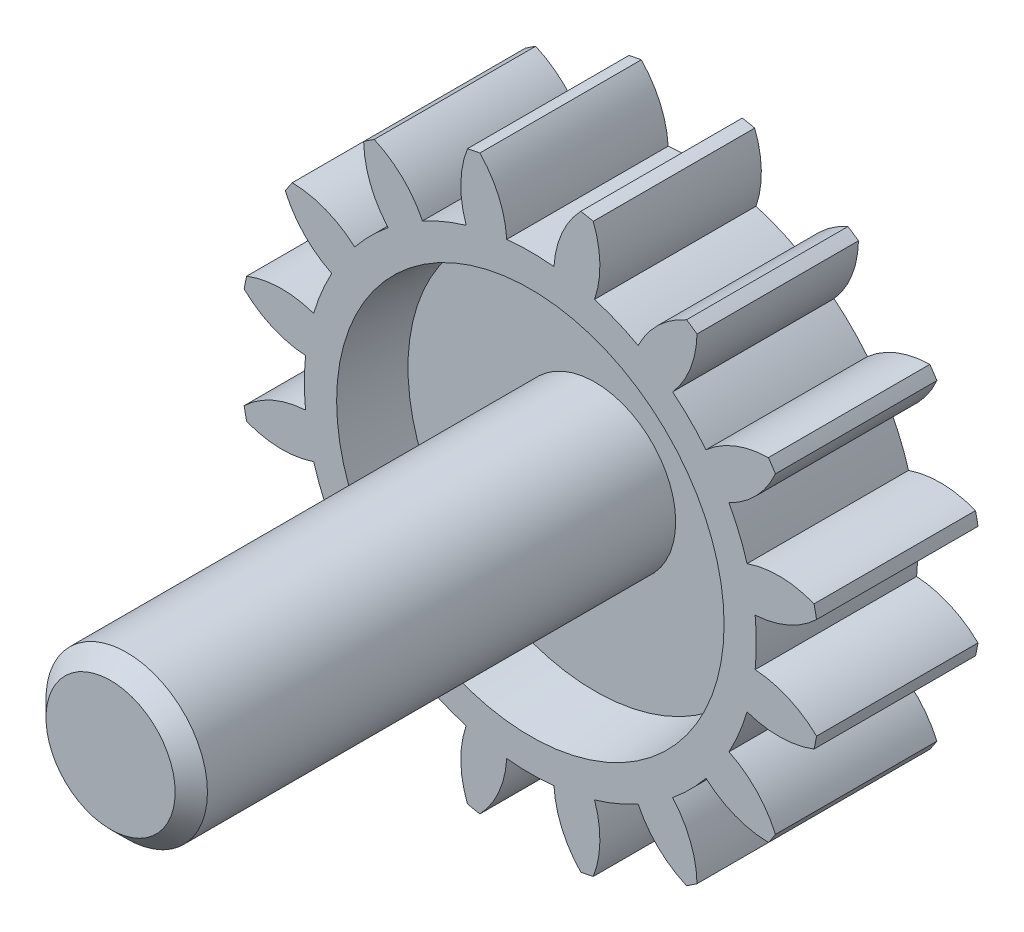
SolidWorks part; units mm, degrees
ref_plane "Спереди" through (0, 0, 0) normal (0, 0, 1) x (1, 0, 0)
ref_plane "Сверху" through (0, 0, 0) normal (0, 1, 0) x (1, 0, 0)
ref_plane "Справа" through (0, 0, 0) normal (1, 0, 0) x (0, 0, -1)
sketch "Эскиз1" plane through (0, 0, 0) normal (0, 0, 1) x (1, 0, 0)
  circle A0 centre (0, 0) radius 18
  dimension "D1" = 36
extrude "Бобышка-Вытянуть1" add sketch "Эскиз1" against normal blind 10
sketch "Эскиз2" plane through (0, 0, 0) normal (0, 0, 1) x (1, 0, 0)
  line L0 (0, 0) -> (0, 18) construction
  line L1 (0, 0) -> (-3.1257, 17.7265) construction
  line L2 (0, 0) -> (-1.8815, 17.9014) construction
  circle A0 centre (0, 0) radius 18 construction
  arc A1 (3.1257, 17.7265) -> (-3.1257, 17.7265) centre (0, 0) ccw
  arc A2 (1.4634, 13.9233) -> (-1.4634, 13.9233) centre (0, 0) ccw
  arc A3 (-3.1257, 17.7265) -> (-1.4634, 13.9233) centre (-7.453, 13.5703) cw
  arc A4 (3.1257, 17.7265) -> (1.4634, 13.9233) centre (7.453, 13.5703) ccw
  point P8 (0, 0)
  dimension "D1" = 10
  dimension "D3" = 6
  dimension "D2" = 6
  dimension "D4" = 14
extrude "Вырез-Вытянуть1" cut sketch "Эскиз2" against normal through all
pattern_circular "Круговой массив1" count 16 over 360 about axis through (0, 0, -10) along (0, 0, 1) of "Вырез-Вытянуть1" reverse direction yes
sketch "Эскиз3" plane through (0, 0, 0) normal (0, 0, 1) x (1, 0, 0)
  circle A0 centre (0, 0) radius 12
  dimension "D1" = 24
extrude "Вырез-Вытянуть2" cut sketch "Эскиз3" against normal blind 4 draft 6
extrude "Вырез-Вытянуть3" cut sketch "Эскиз3<2>" along normal blind 4 draft 6 from surface starting at face at (0, 0, -10)
sketch "Эскиз3<2>" plane through (0, 0, 0) normal (0, 0, 1) x (1, 0, 0) same geometry as "Эскиз3"
sketch "Эскиз5" plane through (0, 0, -4) normal (0, 0, 1) x (1, 0, 0)
  circle A0 centre (0, 0) radius 5
  dimension "D1" = 10
extrude "Бобышка-Вытянуть2" add sketch "Эскиз5" along normal blind 30
chamfer "Фаска1" distance 1 angle 45 1 edges at (5, 0, 26)
